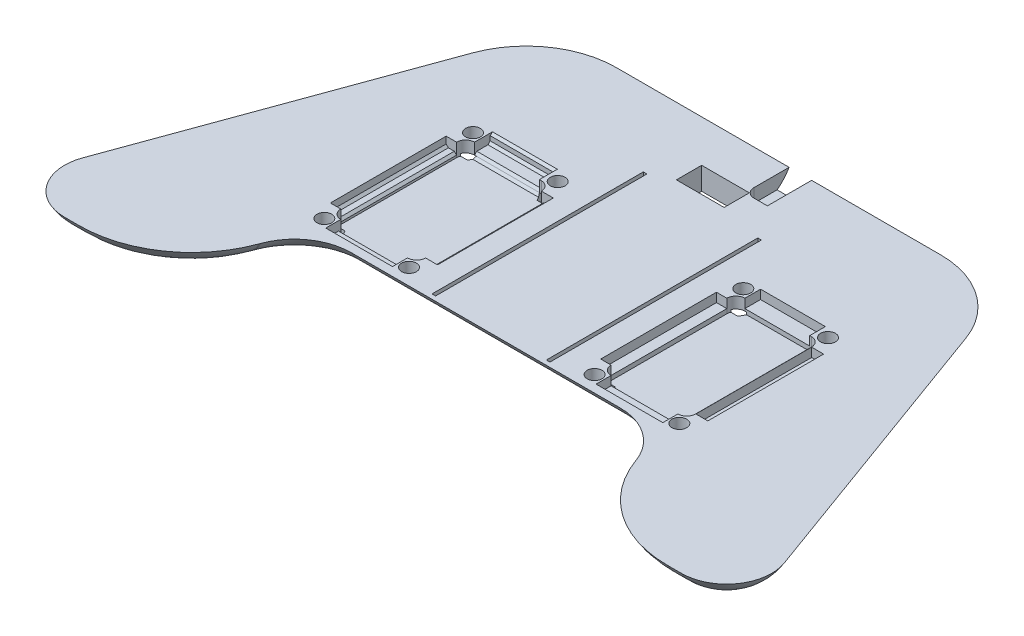
SolidWorks part; units mm, degrees
ref_plane "前视基准面" through (0, 0, 0) normal (0, 0, 1) x (1, 0, 0)
ref_plane "上视基准面" through (0, 0, 0) normal (0, 1, 0) x (1, 0, 0)
ref_plane "右视基准面" through (0, 0, 0) normal (1, 0, 0) x (0, 0, -1)
other "Configuration Table"
sketch "草图1" plane through (0, 0, 0) normal (0, 1, 0) x (1, 0, 0)
  line L0 (0, 0) -> (0, 65)
  line L2 (-35.9958, 65) -> (35.9958, 65)
  line L3 (54.7897, 51.8404) -> (77.8728, -11.5798)
  line L4 (68.4758, -25) -> (65.2625, -25)
  line L5 (41.7702, -8.5505) -> (41.6753, -8.2899)
  line L7 (29.8361, 0) -> (-29.8361, 0)
  line L8 (-41.7702, -8.5505) -> (-41.6753, -8.2899)
  line L9 (-68.4758, -25) -> (-65.2625, -25)
  line L10 (-54.7897, 51.8404) -> (-77.8728, -11.5798)
  arc A1 (65.2625, -25) -> (41.7702, -8.5505) centre (65.2625, 0) cw
  arc A2 (41.6753, -8.2899) -> (29.8361, 0) centre (29.8361, -12.599) ccw
  arc A3 (35.9958, 65) -> (54.7897, 51.8404) centre (35.9958, 45) cw
  arc A4 (77.8728, -11.5798) -> (68.4758, -25) centre (68.4758, -15) cw
  arc A5 (-77.8728, -11.5798) -> (-68.4758, -25) centre (-68.4758, -15) ccw
  arc A6 (-35.9958, 65) -> (-54.7897, 51.8404) centre (-35.9958, 45) ccw
  arc A7 (-41.6753, -8.2899) -> (-29.8361, 0) centre (-29.8361, -12.599) cw
  arc A8 (-65.2625, -25) -> (-41.7702, -8.5505) centre (-65.2625, 0) ccw
  point P9 (0, 65)
  point P10 (47.7573, -25)
  point P15 (50, 65)
  point P18 (82.7573, -25)
  point P31 (-82.7573, -25)
  point P32 (-50, 65)
  point P33 (-47.7573, -25)
  dimension "D6" = 25
  dimension "D7" = 20
  dimension "D8" = 10
  dimension "D9" = 25
  dimension "D1" = 65
  dimension "D2" = 70
  dimension "D3" = 50
  dimension "D4" = 35
  dimension "D5" = 70
extrude "凸台-拉伸1" add sketch "草图1" along normal blind 5 contours L9 A8 L8 A7 L7 L0 L2 A6 L10 A5 | A4 L3 A3 L2 L0 L7 A2 L5 A1 L4 region at (-35.8986, 0, -23.3393) region at (35.8986, 0, -23.3393)
fillet "圆角1" radius 10 16 edges at (-50.9231, 0, 20.4788) (-41.7228, 0, 8.4202) (-37.0626, 0, 2.2785) (0, 0, 0) (37.0626, 0, 2.2785) (41.7228, 0, 8.4202) (50.9231, 0, 20.4788) (66.8692, 0, 25) (76.6674, 0, 20.7358) (66.3312, 0, -20.1303) (47.4674, 0, -61.383) (0, 0, -65) (-47.4674, 0, -61.383) (-66.3312, 0, -20.1303) (-76.6674, 0, 20.7358) (-66.8692, 0, 25)
sketch "草图2" plane through (0, 5, 0) normal (0, 1, 0) x (1, 0, 0)
  line L0 (0, 65) -> (0, 0) construction
  line L1 (-35.9958, 65) -> (35.9958, 65) construction
  line L2 (0, 32.5) -> (-15, 32.5) construction
  line L3 (0, 32.5) -> (15, 32.5) construction
  dimension "D1" = 15
  dimension "D2" = 15
sketch "草图3" plane through (0, 5, 0) normal (0, 1, 0) x (1, 0, 0)
  line L1 (-7.25, 55.1813) -> (2.35, 55.1813)
  line L2 (-7.25, 55.1813) -> (-7.25, 50.5813)
  line L3 (-7.25, 50.5813) -> (2.35, 50.5813)
  line L4 (2.35, 55.1813) -> (2.35, 50.5813)
  circle A0 centre (-39.4, 36.5813) radius 1.65
  circle A1 centre (-20.6, 36.5813) radius 1.65
  circle A2 centre (20.6, 36.5813) radius 1.65
  circle A4 centre (-39.4, 3.5813) radius 1.65
  circle A5 centre (-20.6, 3.5813) radius 1.65
  circle A6 centre (20.6, 3.5813) radius 1.65
  circle A8 centre (39.4, 36.5813) radius 1.65
  circle A9 centre (39.4, 3.5813) radius 1.65
extrude "切除-拉伸1" cut sketch "草图3" against normal through all
sketch "草图4" plane through (0, 5, 0) normal (0, 1, 0) x (1, 0, 0)
  line L0 (-35.9958, 65) -> (35.9958, 65) construction
  line L1 (4.35, 55.1813) -> (7.35, 55.1813)
  line L2 (2.35, 57.1813) -> (2.35, 65)
  line L3 (2.35, 65) -> (7.35, 65)
  line L4 (7.35, 55.1813) -> (7.35, 65)
  line L6 (-37.4, 34.9313) -> (-22.5849, 34.9313)
  line L7 (-39.4, 32.9313) -> (-39.4, 7.2312)
  line L8 (-37.4, 5.2312) -> (-22.5849, 5.2312)
  line L9 (-20.5849, 32.9313) -> (-20.5849, 7.2312)
  line L10 (22.6, 34.9313) -> (37.3849, 34.9313)
  line L11 (20.6, 32.9313) -> (20.6, 7.2312)
  line L12 (22.6, 5.2312) -> (37.3849, 5.2312)
  line L13 (39.3849, 32.9313) -> (39.3849, 7.2312)
  circle A0 centre (-39.4, 36.5813) radius 1.65 construction
  circle A1 centre (-20.6, 3.5813) radius 1.65 construction
  circle A2 centre (-20.6, 3.5813) radius 1.65 construction
  circle A3 centre (20.6, 36.5813) radius 1.65 construction
  circle A4 centre (39.4, 3.5813) radius 1.65 construction
  arc A5 (37.3849, 5.2312) -> (39.3849, 7.2312) centre (37.3849, 7.2312) ccw
  arc A6 (20.6, 7.2312) -> (22.6, 5.2312) centre (22.6, 7.2312) ccw
  arc A7 (37.3849, 34.9313) -> (39.3849, 32.9313) centre (37.3849, 32.9313) cw
  arc A8 (22.6, 34.9313) -> (20.6, 32.9313) centre (22.6, 32.9313) ccw
  arc A9 (4.35, 55.1813) -> (2.35, 57.1813) centre (4.35, 57.1813) cw
  arc A10 (-22.5849, 5.2312) -> (-20.5849, 7.2312) centre (-22.5849, 7.2312) ccw
  arc A11 (-39.4, 7.2312) -> (-37.4, 5.2312) centre (-37.4, 7.2312) ccw
  arc A12 (-22.5849, 34.9313) -> (-20.5849, 32.9313) centre (-22.5849, 32.9313) cw
  arc A13 (-37.4, 34.9313) -> (-39.4, 32.9313) centre (-37.4, 32.9313) ccw
  point P27 (39.3849, 5.2312)
  point P34 (20.6, 34.9313)
  point P37 (2.35, 55.1813)
  point P40 (-20.5849, 5.2312)
  point P47 (-39.4, 34.9313)
  dimension "D2" = 2
  dimension "D1" = 5
extrude "切除-拉伸4" cut sketch "草图4" against normal blind 3
sketch "草图5" plane through (0, 5, 0) normal (0, 1, 0) x (1, 0, 0)
  line L0 (-12.55, 47.9478) -> (-12.55, 1.0278) construction
  line L1 (-12.55, 47.9478) -> (-12.95, 47.9478)
  line L2 (12.85, 47.9478) -> (12.45, 47.9478)
  line L3 (-12.95, 47.9478) -> (-12.15, 47.9478)
  line L4 (-12.95, 47.9478) -> (-12.95, 1.0278)
  line L5 (-12.95, 1.0278) -> (-12.15, 1.0278)
  line L6 (-12.15, 47.9478) -> (-12.15, 1.0278)
  line L7 (12.45, 47.9478) -> (13.25, 47.9478)
  line L8 (12.45, 47.9478) -> (12.45, 1.0278)
  line L9 (12.45, 1.0278) -> (13.25, 1.0278)
  line L10 (13.25, 47.9478) -> (13.25, 1.0278)
  line L11 (12.85, 47.9478) -> (12.85, 1.0278) construction
  circle A0 centre (-12.55, 47.3478) radius 0.6 construction
  circle A1 centre (-12.55, 1.6278) radius 0.6 construction
  dimension "D1" = 0.4
  dimension "D2" = 0.8
  dimension "D3" = 2
extrude "切除-拉伸5" cut sketch "草图5" against normal through all contours L3 L6 L5 L4 | L7 L10 L9 L8
sketch "草图6" plane through (0, 0, 0) normal (0, -1, 0) x (1, 0, 0)
  line L0 (-12.55, -47.9478) -> (-13.8, -47.9478)
  line L1 (-12.95, -47.9478) -> (-12.15, -47.9478) construction
  line L2 (12.85, -47.9478) -> (11.6, -47.9478)
  line L3 (-13.8, -47.9478) -> (-11.3, -47.9478)
  line L4 (-13.8, -47.9478) -> (-13.8, -1.0173)
  line L5 (-13.8, -1.0173) -> (-11.3, -1.0173)
  line L6 (-11.3, -47.9478) -> (-11.3, -1.0173)
  line L7 (11.6, -47.9478) -> (14.1, -47.9478)
  line L8 (11.6, -47.9478) -> (11.6, -1.0173)
  line L9 (11.6, -1.0173) -> (14.1, -1.0173)
  line L10 (14.1, -47.9478) -> (14.1, -1.0173)
  dimension "D1" = 1.25
  dimension "D2" = 2.5
  dimension "D3" = 2
extrude "切除-拉伸6" cut sketch "草图6" against normal blind 2 contours L3 L6 L5 L4 | L8 L9 L10 L7
sketch "草图7" plane through (0, 0, 0) normal (0, -1, 0) x (1, 0, 0)
  line L0 (-17.2514, -36.5813) -> (-18.9257, -33.6813)
  line L1 (-36.0514, -36.5813) -> (-37.7257, -33.6813)
  line L2 (-37.7257, -33.6813) -> (-41.0743, -33.6813)
  line L3 (-41.0743, -33.6813) -> (-42.7486, -36.5813)
  line L4 (-42.7486, -36.5813) -> (-41.0743, -39.4813)
  line L5 (-41.0743, -39.4813) -> (-37.7257, -39.4813)
  line L6 (-37.7257, -39.4813) -> (-36.0514, -36.5813)
  line L7 (-18.9257, -33.6813) -> (-22.2743, -33.6813)
  line L8 (-22.2743, -33.6813) -> (-23.9486, -36.5813)
  line L9 (-23.9486, -36.5813) -> (-22.2743, -39.4813)
  line L10 (-22.2743, -39.4813) -> (-18.9257, -39.4813)
  line L11 (-18.9257, -39.4813) -> (-17.2514, -36.5813)
  line L12 (-17.2514, -3.5813) -> (-18.9257, -0.6813)
  line L13 (-18.9257, -0.6813) -> (-22.2743, -0.6813)
  line L14 (-22.2743, -0.6813) -> (-23.9486, -3.5813)
  line L15 (-23.9486, -3.5813) -> (-22.2743, -6.4813)
  line L16 (-22.2743, -6.4813) -> (-18.9257, -6.4813)
  line L17 (-18.9257, -6.4813) -> (-17.2514, -3.5813)
  line L18 (-36.0514, -3.5813) -> (-37.7257, -0.6813)
  line L19 (-37.7257, -0.6813) -> (-41.0743, -0.6813)
  line L20 (-41.0743, -0.6813) -> (-42.7486, -3.5813)
  line L21 (-42.7486, -3.5813) -> (-41.0743, -6.4813)
  line L22 (-41.0743, -6.4813) -> (-37.7257, -6.4813)
  line L23 (-37.7257, -6.4813) -> (-36.0514, -3.5813)
  line L24 (42.7486, -36.5813) -> (41.0743, -33.6813)
  line L25 (23.9486, -36.5813) -> (22.2743, -33.6813)
  line L26 (22.2743, -33.6813) -> (18.9257, -33.6813)
  line L27 (18.9257, -33.6813) -> (17.2514, -36.5813)
  line L28 (17.2514, -36.5813) -> (18.9257, -39.4813)
  line L29 (18.9257, -39.4813) -> (22.2743, -39.4813)
  line L30 (22.2743, -39.4813) -> (23.9486, -36.5813)
  line L31 (41.0743, -33.6813) -> (37.7257, -33.6813)
  line L32 (37.7257, -33.6813) -> (36.0514, -36.5813)
  line L33 (36.0514, -36.5813) -> (37.7257, -39.4813)
  line L34 (37.7257, -39.4813) -> (41.0743, -39.4813)
  line L35 (41.0743, -39.4813) -> (42.7486, -36.5813)
  line L36 (42.7486, -3.5813) -> (41.0743, -0.6813)
  line L37 (41.0743, -0.6813) -> (37.7257, -0.6813)
  line L38 (37.7257, -0.6813) -> (36.0514, -3.5813)
  line L39 (36.0514, -3.5813) -> (37.7257, -6.4813)
  line L40 (37.7257, -6.4813) -> (41.0743, -6.4813)
  line L41 (41.0743, -6.4813) -> (42.7486, -3.5813)
  line L42 (23.9486, -3.5813) -> (22.2743, -0.6813)
  line L43 (22.2743, -0.6813) -> (18.9257, -0.6813)
  line L44 (18.9257, -0.6813) -> (17.2514, -3.5813)
  line L45 (17.2514, -3.5813) -> (18.9257, -6.4813)
  line L46 (18.9257, -6.4813) -> (22.2743, -6.4813)
  line L47 (22.2743, -6.4813) -> (23.9486, -3.5813)
  circle A0 centre (-39.4, -36.5813) radius 2.9 construction
  circle A1 centre (-20.6, -36.5813) radius 2.9 construction
  circle A2 centre (-20.6, -3.5813) radius 2.9 construction
  circle A3 centre (-39.4, -3.5813) radius 2.9 construction
  circle A4 centre (20.6, -36.5813) radius 2.9 construction
  circle A5 centre (39.4, -36.5813) radius 2.9 construction
  circle A6 centre (39.4, -3.5813) radius 2.9 construction
  circle A7 centre (20.6, -3.5813) radius 2.9 construction
  dimension "D1" = 2
  dimension "D2" = 2
  dimension "D3" = 2
extrude "切除-拉伸7" cut sketch "草图7" against normal blind 2.5
sketch "草图8" plane through (0, 5, 0) normal (0, 1, 0) x (1, 0, 0)
  line L0 (-7.25, 50.5813) -> (-2.45, 52.8813) construction
  line L1 (-2.45, 52.8813) -> (-2.45, 50.5813) construction
  line L2 (-7.25, 50.5813) -> (2.35, 50.5813) construction
  line L3 (2.35, 50.5813) -> (2.35, 55.1813) construction
  line L4 (-7.75, 55.6813) -> (2.85, 55.6813)
  line L5 (-7.75, 55.6813) -> (-7.75, 50.0813)
  line L6 (-7.75, 50.0813) -> (2.85, 50.0813)
  line L7 (2.85, 55.6813) -> (2.85, 50.0813)
  line L8 (-7.75, 55.6813) -> (2.85, 50.0813) construction
  line L9 (-7.75, 50.0813) -> (2.85, 55.6813) construction
  line L10 (-7.25, 55.1813) -> (-7.25, 50.5813) construction
  line L11 (2.35, 55.1813) -> (-7.25, 55.1813) construction
  dimension "D1" = 0.5
  dimension "D2" = 0.5
  dimension "D3" = 0.5
  dimension "D4" = 0.5
extrude "切除-拉伸8" cut sketch "草图8" against normal through all
sketch "草图9" plane through (0, 5, 0) normal (0, 1, 0) x (1, 0, 0)
  line L1 (-39.4, 32.9313) -> (-41.7068, 32.9313)
  line L2 (-39.4, 32.9313) -> (-39.4, 7.2312)
  line L3 (-39.4, 7.2312) -> (-41.7068, 7.2312)
  line L4 (-41.7068, 32.9313) -> (-41.7068, 7.2312)
  line L5 (-37.4, 34.9313) -> (-23.0106, 34.9313)
  line L6 (-37.4, 34.9313) -> (-37.4, 38.4087)
  line L7 (-37.4, 38.4087) -> (-23.0106, 38.4087)
  line L8 (-23.0106, 34.9313) -> (-23.0106, 38.4087)
  line L9 (-20.5849, 32.9313) -> (-17.9218, 32.9313)
  line L10 (-20.5849, 32.9313) -> (-20.5849, 7.2312)
  line L11 (-20.5849, 7.2312) -> (-17.9218, 7.2312)
  line L12 (-17.9218, 32.9313) -> (-17.9218, 7.2312)
  line L13 (-22.5849, 5.2312) -> (-37.4, 5.2312)
  line L14 (-22.5849, 5.2312) -> (-22.5849, 1.9014)
  line L15 (-22.5849, 1.9014) -> (-37.4, 1.9014)
  line L16 (-37.4, 5.2312) -> (-37.4, 1.9014)
  point P0 (-39.4, 7.2312)
  point P1 (-39.4, 32.9313)
  point P2 (-20.5849, 32.9313)
  point P3 (-20.5849, 7.2312)
extrude "切除-拉伸9" cut sketch "草图9" against normal blind 2
chamfer "倒角1" distance 0.5 angle 45 11 edges at (-30, 2, -34.9313) (-30, 2, -5.2312) (-29.9925, 3, -1.9014) (-29.9925, 3, -5.2312) (-30.2053, 5, -38.4087) (-30.2053, 3, -38.4087) (-17.9218, 3, -20.0813) (-20.5849, 3, -20.0813) (-41.7068, 3, -20.0813) (-39.4, 3, -20.0813) (-30.2053, 3, -34.9313)
pattern_linear "阵列(线性)3" count 2 spacing 60 along (1, 0, 0) of "切除-拉伸9"
